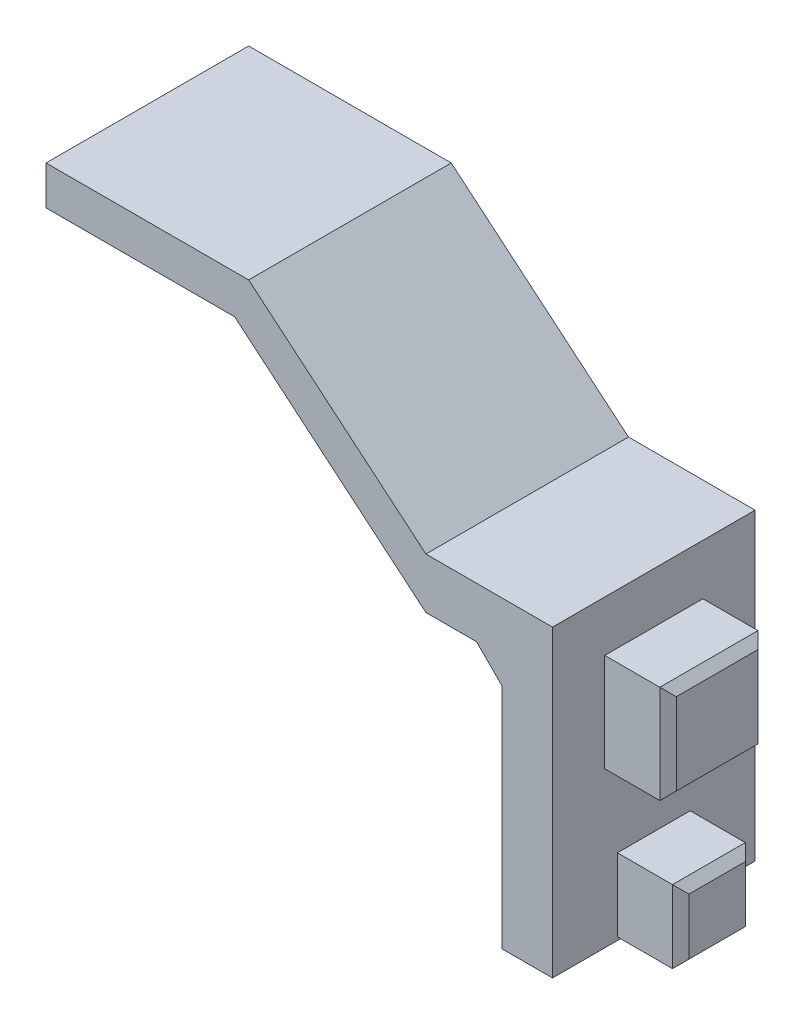
SolidWorks part; units mm, degrees
ref_plane "Front Plane" through (0, 0, 0) normal (0, 0, 1) x (1, 0, 0)
ref_plane "Top Plane" through (0, 0, 0) normal (0, 1, 0) x (1, 0, 0)
ref_plane "Right Plane" through (0, 0, 0) normal (1, 0, 0) x (0, 0, -1)
sketch "Sketch1" plane through (0, 0, 0) normal (0, 0, 1) x (1, 0, 0)
  line L0 (0, 0) -> (0, 12)
  line L1 (0, 12) -> (-5, 12)
  line L2 (-5, 12) -> (-5, 10)
  line L3 (-5, 10) -> (-3, 10)
  line L4 (-2, 9) -> (-2, 0)
  line L5 (-2, 0) -> (0, 0)
  line L6 (-3, 10) -> (-2, 9)
  line L7 (0, 10) -> (2.5, 10)
  line L8 (2.5, 10) -> (2.5, 6.125)
  line L9 (2.5, 6.125) -> (0, 6.125)
  line L10 (0, 3) -> (2.5, 3)
  line L11 (2.5, 3) -> (2.5, 0.125)
  line L12 (2.5, 0.125) -> (0, 0.125)
  line L13 (-5, 12) -> (-12, 17.8737)
  line L14 (-12, 17.8737) -> (-20, 17.8737)
  line L15 (-20, 17.8737) -> (-20, 16.3358)
  line L16 (-20, 16.3358) -> (-12.5508, 16.3358)
  line L17 (-12.5508, 16.3358) -> (-5, 10)
  point P6 (-2, 10)
  point P15 (2.5, 8.0625)
  point P18 (2.5, 1.5625)
  dimension "D1" = 12
  dimension "D2" = 5
  dimension "D3" = 2
  dimension "D4" = 2.5
  dimension "D5" = 3.875
  dimension "D6" = 3.125
  dimension "D8" = 2
  dimension "D9" = 2.875
  dimension "D10" = 2
  dimension "D11" = 2.5
  dimension "D12" = 8
  dimension "D13" = 15
  dimension "D14" = 140
extrude "Boss-Extrude1" add sketch "Sketch1" against normal mid plane 8 contours L3 L6 L4 L5 L0 L1 L2 | L16 L17 L2 L13 L14 L15 region at (-1.5137, 7.0437, 0) region at (-8.6665, 13.2977, 0)
extrude "Boss-Extrude2" add sketch "Sketch1<3>" along normal mid plane 3.875 contours L9 L8 L7 L0 region at (1.25, 8.0625, 0)
sketch "Sketch1<3>" plane through (0, 0, 0) normal (0, 0, 1) x (1, 0, 0) same geometry as "Sketch1"
extrude "Boss-Extrude3" add sketch "Sketch1<4>" along normal mid plane 2.875 contours L12 L11 L10 L0 region at (1.25, 1.5625, 0)
sketch "Sketch1<4>" plane through (0, 0, 0) normal (0, 0, 1) x (1, 0, 0) same geometry as "Sketch1"
chamfer "Chamfer1" distance 0.325 angle 45 8 edges at (2.5, 0.125, 0) (2.5, 1.5625, 1.4375) (2.5, 3, 0) (2.5, 1.5625, -1.4375) (2.5, 6.125, 0) (2.5, 8.0625, 1.9375) (2.5, 10, 0) (2.5, 8.0625, -1.9375)
